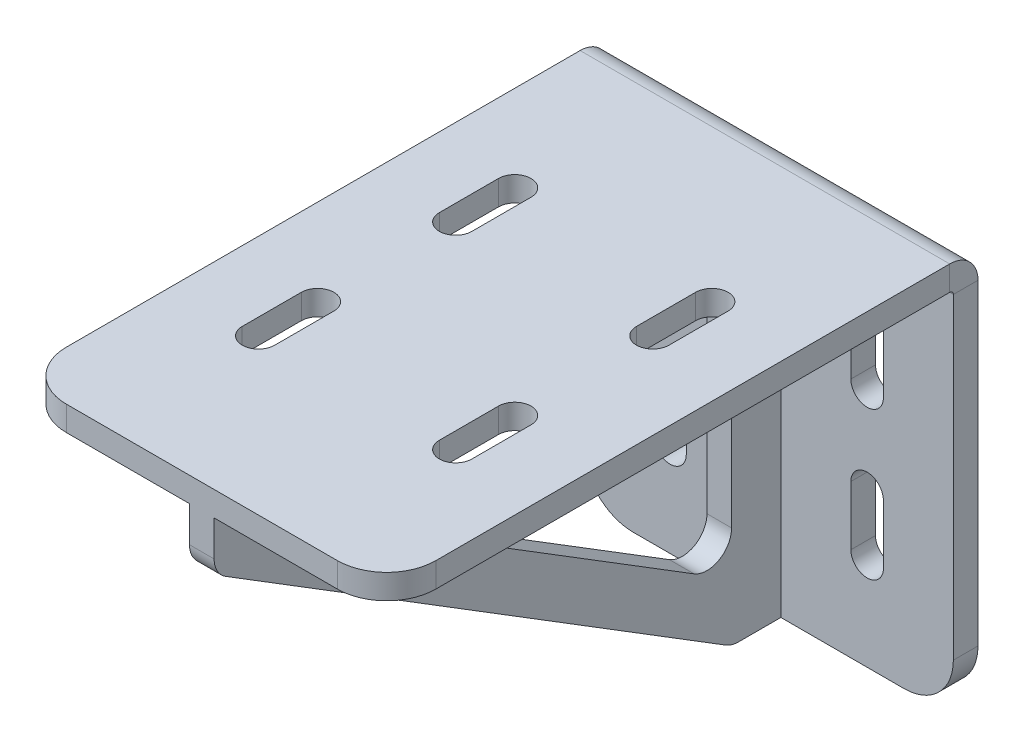
SolidWorks part; units mm, degrees
note: The reader was unsure of these and kept them because the rebuilt part matched: flange length of "边线-法兰1".
ref_plane "前视基准面" through (0, 0, 0) normal (0, 0, 1) x (1, 0, 0)
ref_plane "上视基准面" through (0, 0, 0) normal (0, 1, 0) x (1, 0, 0)
ref_plane "右视基准面" through (0, 0, 0) normal (1, 0, 0) x (0, 0, -1)
sketch "草图1" plane through (0, 0, 0) normal (0, 0, 1) x (1, 0, 0)
  line L1 (-37.5, 40) -> (37.5, 40)
  line L2 (-37.5, 40) -> (-37.5, -40)
  line L3 (-37.5, -40) -> (37.5, -40)
  line L4 (37.5, 40) -> (37.5, -40)
  line L5 (-37.5, 40) -> (37.5, -40) construction
  line L6 (-37.5, -40) -> (37.5, 40) construction
  point P0 (0, 0)
  dimension "D1" = 75
  dimension "D2" = 80
base flange "基体-法兰1" sketch "草图1" thickness 5 reverse thickness direction no parameters "D1"=0.7366
edge flange "边线-法兰1" sketch "草图8" flange angle 90 flange length 120 flange position material inside bend radius 0.7366 thickness 5 relief rectangular parameters "D6"=10
sketch "草图8" plane through (0, 40, 0) normal (0, 1, 0) x (-1, 0, 0)
  line L0 (-37.5, 0) -> (37.5, 0) construction
  line L1 (-37.5, 0) -> (37.5, 0)
  line L2 (-37.5, 0) -> (-37.5, 115)
  line L3 (-37.5, 115) -> (37.5, 115)
  line L4 (37.5, 115) -> (37.5, 0)
bend "边线折弯1" bend radius 0.7366 bend angle 90 parameters "D5"=1
sketch "草图9" plane through (0, 0, 0) normal (1, 0, 0) x (0, 0, -1)
  line L0 (-115, 35) -> (-115, 25)
  line L1 (-115, 25) -> (-10, -40)
  line L2 (-10, -40) -> (0, -40)
  line L3 (-115, 35) -> (-0.7366, 35) construction
  line L4 (0, -40) -> (0, 34.2634) construction
  line L5 (-115, 35) -> (-0.7366, 35)
  line L6 (0, -40) -> (0, 34.2634)
  arc A0 (0, 34.2634) -> (-0.7366, 35) centre (-0.7366, 34.2634) ccw construction
  arc A1 (0, 34.2634) -> (-0.7366, 35) centre (-0.7366, 34.2634) ccw
  dimension "D1" = 10
extrude "凸台-拉伸1" add sketch "草图9" along normal mid plane 5
sketch "草图10" plane through (2.5, 0, 0) normal (1, 0, 0) x (0, 0, -1)
  line L10 (-10, 25) -> (-96.0014, 25)
  line L11 (-96.0014, 25) -> (-10, -28.239)
  line L12 (-10, -28.239) -> (-10, 25)
  line L13 (-10, 25) -> (-96.0014, 25)
  line L14 (-96.0014, 25) -> (-10, -28.239)
  line L15 (-10, -28.239) -> (-10, 25)
  dimension "D1" = 10
extrude "切除-拉伸1" cut sketch "草图10" against normal through all
fillet "圆角1" radius 5 5 edges at (0, -28.239, 10) (0, 25, 10) (0, 25, 96.0014) (0, 25, 115) (0, -40, 10)
fillet "圆角2" radius 10 4 edges at (-37.5, -40, -2.5) (37.5, -40, -2.5) (-37.5, 37.5, 115) (37.5, 37.5, 115)
sketch "草图11" plane through (0, 0, 0) normal (0, 0, 1) x (1, 0, 0)
  line L0 (20, 0) -> (-20, 0) construction
  line L2 (-20, -15) -> (-20, 15) construction
  line L3 (20, -15) -> (20, 15) construction
  line L4 (-20, -9) -> (-20, -21) construction
  line L5 (-16.7, -9) -> (-16.7, -21)
  line L6 (-23.3, -9) -> (-23.3, -21)
  line L7 (-20, 9) -> (-20, 21) construction
  line L8 (-23.3, 9) -> (-23.3, 21)
  line L9 (-16.7, 9) -> (-16.7, 21)
  line L10 (20, 9) -> (20, 21) construction
  line L11 (16.7, 9) -> (16.7, 21)
  line L12 (23.3, 9) -> (23.3, 21)
  line L13 (20, -9) -> (20, -21) construction
  line L14 (23.3, -9) -> (23.3, -21)
  line L15 (16.7, -9) -> (16.7, -21)
  arc A0 (-16.7, -9) -> (-23.3, -9) centre (-20, -9) ccw
  arc A1 (-23.3, -21) -> (-16.7, -21) centre (-20, -21) ccw
  arc A2 (-23.3, 9) -> (-16.7, 9) centre (-20, 9) ccw
  arc A3 (-16.7, 21) -> (-23.3, 21) centre (-20, 21) ccw
  arc A4 (16.7, 9) -> (23.3, 9) centre (20, 9) ccw
  arc A5 (23.3, 21) -> (16.7, 21) centre (20, 21) ccw
  arc A6 (23.3, -9) -> (16.7, -9) centre (20, -9) ccw
  arc A7 (16.7, -21) -> (23.3, -21) centre (20, -21) ccw
  point P3 (0, 0)
  point P6 (-20, 0)
  point P10 (20, 0)
  point P12 (-20, -15)
  point P18 (-20, 15)
  point P25 (20, 15)
  point P32 (20, -15)
  dimension "D1" = 40
  dimension "D2" = 30
  dimension "D3" = 6.6
  dimension "D4" = 12
extrude "切除-拉伸2" cut sketch "草图11" against normal through all
sketch "草图12" plane through (0, 35, 0) normal (0, -1, 0) x (1, 0, 0)
  line L0 (0, 115) -> (0, 0) construction
  line L1 (37.5, 115) -> (-37.5, 115) construction
  line L2 (-20, 57.5) -> (20, 57.5) construction
  line L3 (-20, 37.5) -> (-20, 77.5) construction
  line L4 (20, 37.5) -> (20, 77.5) construction
  line L5 (-20, 83.5) -> (-20, 71.5) construction
  line L6 (-16.7, 83.5) -> (-16.7, 71.5)
  line L7 (-23.3, 83.5) -> (-23.3, 71.5)
  line L8 (20, 83.5) -> (20, 71.5) construction
  line L9 (23.3, 83.5) -> (23.3, 71.5)
  line L10 (16.7, 83.5) -> (16.7, 71.5)
  line L11 (20, 31.5) -> (20, 43.5) construction
  line L12 (16.7, 31.5) -> (16.7, 43.5)
  line L13 (23.3, 31.5) -> (23.3, 43.5)
  line L14 (-20, 31.5) -> (-20, 43.5) construction
  line L15 (-23.3, 31.5) -> (-23.3, 43.5)
  line L16 (-16.7, 31.5) -> (-16.7, 43.5)
  arc A0 (-16.7, 83.5) -> (-23.3, 83.5) centre (-20, 83.5) ccw
  arc A1 (-23.3, 71.5) -> (-16.7, 71.5) centre (-20, 71.5) ccw
  arc A2 (23.3, 83.5) -> (16.7, 83.5) centre (20, 83.5) ccw
  arc A3 (16.7, 71.5) -> (23.3, 71.5) centre (20, 71.5) ccw
  arc A4 (16.7, 31.5) -> (23.3, 31.5) centre (20, 31.5) ccw
  arc A5 (23.3, 43.5) -> (16.7, 43.5) centre (20, 43.5) ccw
  arc A6 (-23.3, 31.5) -> (-16.7, 31.5) centre (-20, 31.5) ccw
  arc A7 (-16.7, 43.5) -> (-23.3, 43.5) centre (-20, 43.5) ccw
  point P8 (0, 57.5)
  point P11 (-20, 57.5)
  point P14 (20, 57.5)
  point P16 (-20, 77.5)
  point P22 (20, 77.5)
  point P29 (20, 37.5)
  point P36 (-20, 37.5)
  dimension "D1" = 40
  dimension "D2" = 40
  dimension "D3" = 12
  dimension "D4" = 6.6
extrude "切除-拉伸3" cut sketch "草图12" against normal through all
sketch "折弯-线1" plane through (0, 0, 0) normal (0, 1, 0) x (1, 0, 0)
sketch "边界框1" plane through (0, 0, 0) normal (0, 1, 0) x (1, 0, 0)
sheet metal parameters "钣金6" thickness 5 parameters "D1"=0.7366
flat pattern "平板型式6" [suppressed]
sketch "折弯-线2" plane through (0, 0, 0) normal (0, 1, 0) x (1, 0, 0)
sketch "边界框2" [suppressed] plane through (0, 0, 0) normal (0, 1, 0) x (1, 0, 0)
sheet metal parameters "钣金7" thickness 5 parameters "D1"=0.7366
flat pattern "平板型式6" [suppressed]
sketch "折弯-线2" plane through (0, 0, 0) normal (0, 1, 0) x (1, 0, 0)
sketch "边界框2" [suppressed] plane through (0, 0, 0) normal (0, 1, 0) x (1, 0, 0)
bend of the flat pattern "展平-<边线折弯1>1"
sheet metal parameters "钣金8" thickness 5 parameters "D1"=0.7366
flat pattern "平板型式6" [suppressed]
sketch "折弯-线2" plane through (0, 0, 0) normal (0, 1, 0) x (1, 0, 0)
sketch "边界框2" [suppressed] plane through (0, 0, 0) normal (0, 1, 0) x (1, 0, 0)
bend of the flat pattern "展平-<边线折弯1>1"
sheet metal parameters "钣金9" thickness 5 parameters "D1"=0.7366
flat pattern "平板型式6" [suppressed]
sketch "折弯-线2" plane through (0, 0, 0) normal (0, 1, 0) x (1, 0, 0)
sketch "边界框2" [suppressed] plane through (0, 0, 0) normal (0, 1, 0) x (1, 0, 0)
bend of the flat pattern "展平-<边线折弯1>1"
sheet metal parameters "钣金10" thickness 5 parameters "D1"=0.7366
flat pattern "平板型式6" [suppressed]
sketch "折弯-线2" plane through (0, 0, 0) normal (0, 1, 0) x (1, 0, 0)
sketch "边界框2" [suppressed] plane through (0, 0, 0) normal (0, 1, 0) x (1, 0, 0)
bend of the flat pattern "展平-<边线折弯1>1"
sheet metal parameters "钣金11" thickness 5 parameters "D1"=0.7366
flat pattern "平板型式6" [suppressed]
sketch "折弯-线2" plane through (0, 0, 0) normal (0, 1, 0) x (1, 0, 0)
sketch "边界框2" [suppressed] plane through (0, 0, 0) normal (0, 1, 0) x (1, 0, 0)
bend of the flat pattern "展平-<边线折弯1>1"
